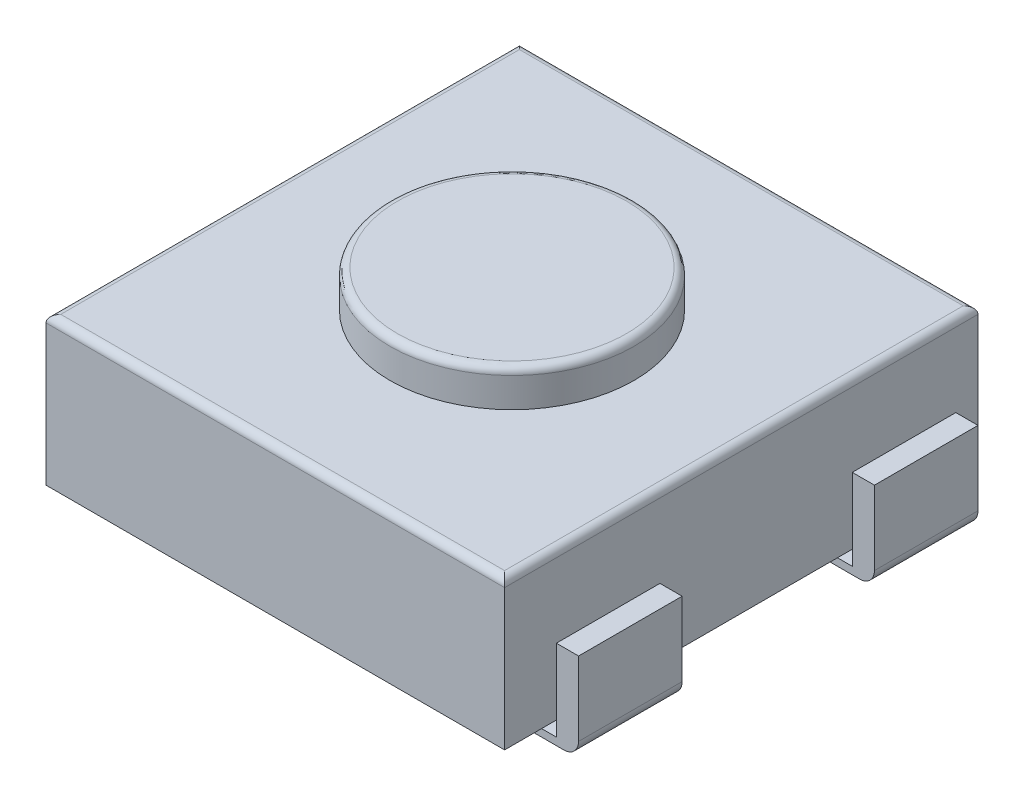
SolidWorks part; units mm, degrees
ref_plane "Plan de face" through (0, 0, 0) normal (0, 0, 1) x (1, 0, 0)
ref_plane "Plan de dessus" through (0, 0, 0) normal (0, 1, 0) x (1, 0, 0)
ref_plane "Plan de droite" through (0, 0, 0) normal (1, 0, 0) x (0, 0, -1)
sketch "Esquisse1" plane through (0, 0, 0) normal (0, 1, 0) x (1, 0, 0)
  line L0 (-3.1, 3.2) -> (3.1, -3.2) construction
  line L1 (-3.1, 3.2) -> (3.1, 3.2)
  line L2 (-3.1, 3.2) -> (-3.1, -3.2)
  line L3 (-3.1, -3.2) -> (3.1, -3.2)
  line L4 (3.1, 3.2) -> (3.1, -3.2)
  point P4 (0, 0)
  dimension "D1" = 6.2
  dimension "D2" = 6.4
extrude "Boss.-Extru.1" add sketch "Esquisse1" along normal blind 2
sketch "Esquisse2" plane through (0, 2, 0) normal (0, 1, 0) x (1, 0, 0)
  circle A0 centre (0, 0) radius 1.65
  dimension "D1" = 3.3
extrude "Boss.-Extru.2" add sketch "Esquisse2" along normal blind 0.5
sketch "Esquisse4" plane through (0, 0, 0) normal (0, 0, 1) x (1, 0, 0)
  line L0 (-3.1, 0) -> (3.1, 0) construction
  line L1 (2.4, 1.1) -> (3.6, 1.1)
  line L2 (2.4, 1.1) -> (2.4, -0.1)
  line L3 (2.4, -0.1) -> (3.6, -0.1)
  line L4 (3.6, 1.1) -> (3.6, -0.1)
  line L5 (0, -1.375) -> (0, 1.375) construction
  line L6 (2.4, 1.1) -> (3.1, 1.1)
  line L7 (2.4, 1.1) -> (2.4, 0)
  line L8 (2.4, 0) -> (3.1, 0)
  line L9 (3.1, 1.1) -> (3.1, 0)
  line L10 (2.4, 1.1) -> (3.3, 1.1)
  line L11 (2.4, 1.1) -> (2.4, 0)
  line L12 (2.4, 0) -> (3.3, 0)
  line L13 (3.3, 1.1) -> (3.3, 0)
  line L14 (-2.4, 0) -> (-3.3, 0)
  line L15 (-3.3, 1.1) -> (-3.3, 0)
  line L16 (-2.4, -0.1) -> (-3.6, -0.1)
  line L17 (-3.6, 1.1) -> (-3.6, -0.1)
  line L18 (-2.4, 1.1) -> (-3.6, 1.1)
  line L19 (-2.4, 1.1) -> (-2.4, -0.1)
  dimension "D1" = 1.2
  dimension "D2" = 1.2
  dimension "D3" = 3.6
  dimension "D4" = 0.1
  dimension "D5" = 0.3
extrude "Boss.-Extru.4" add sketch "Esquisse4" along normal blind 1.4 from offset 1.3 contours L1 L13 L12 L8 L2 L3 L4 | L19 L14 L15 L18 L17 L16 region at (3.33, 0.39, 0) region at (-3.33, 0.39, 0)
fillet "Congé2" radius 0.2 4 edges at (-2.4, -0.1, 2) (2.4, -0.1, 2) (3.6, -0.1, 2) (-3.6, -0.1, 2)
mirror "Symétrie2" about plane through (0, 0, 0) normal (0, 0, 1) of "Congé2", "Boss.-Extru.4"
fillet "Congé3" radius 0.1 1 edges at (0, 2.5, 1.65)
fillet "Congé4" radius 0.1 4 edges at (3.1, 2, 0) (0, 2, 3.2) (-3.1, 2, 0) (0, 2, -3.2)
